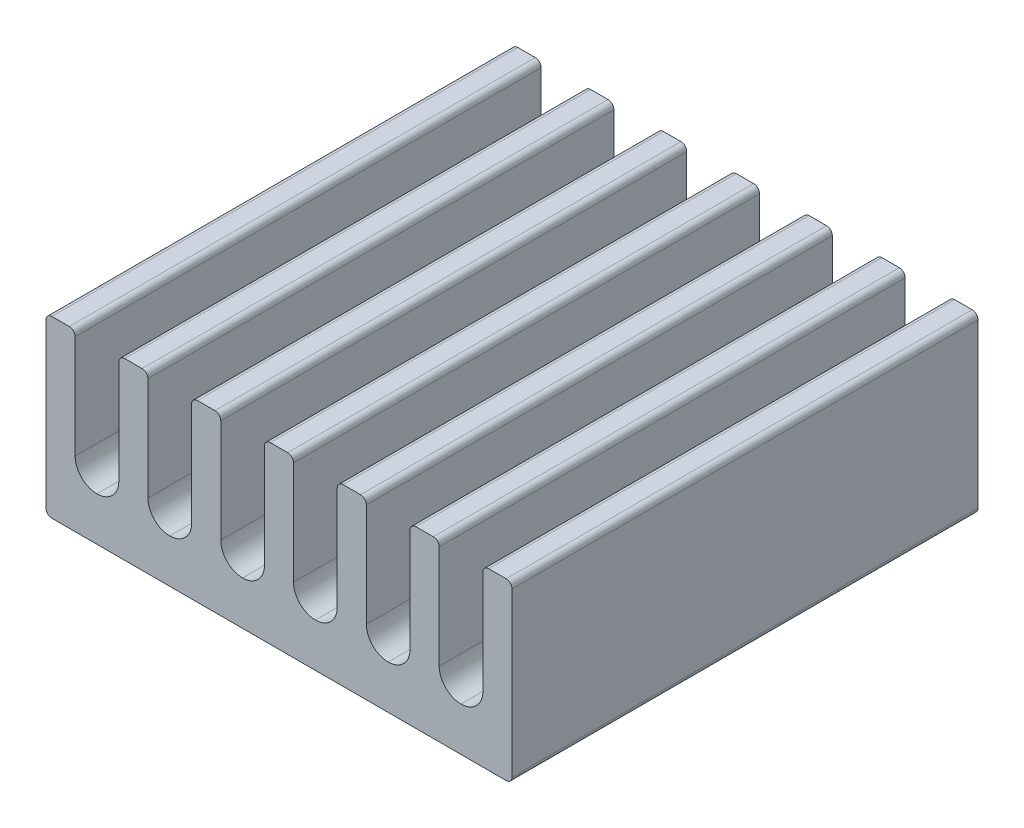
SolidWorks part; units mm, degrees
ref_plane "Front Plane" through (0, 0, 0) normal (0, 0, 1) x (1, 0, 0)
ref_plane "Top Plane" through (0, 0, 0) normal (0, 1, 0) x (1, 0, 0)
ref_plane "Right Plane" through (0, 0, 0) normal (1, 0, 0) x (0, 0, -1)
sketch "Sketch2" plane through (0, 0, 0) normal (0, 1, 0) x (1, 0, 0)
  line L1 (-8, -8) -> (8, -8)
  line L2 (-8, -8) -> (-8, 8)
  line L3 (-8, 8) -> (8, 8)
  line L4 (8, -8) -> (8, 8)
  line L5 (-8, -8) -> (8, 8) construction
  line L6 (-8, 8) -> (8, -8) construction
  point P0 (0, 0)
  dimension "D1" = 16
extrude "Boss-Extrude1" add sketch "Sketch2" along normal blind 1.5 contours L2 L1 L4 L3
sketch "Sketch3" plane through (0, 0, 8) normal (0, 0, 1) x (1, 0, 0)
  line L0 (-8, 0) -> (8, 0) construction
  line L1 (-8, 1.5) -> (-7, 1.5)
  line L2 (-8, 1.5) -> (-8, 6)
  line L3 (-8, 6) -> (-7, 6)
  line L4 (-7, 1.5) -> (-7, 6)
  line L5 (-5.5, 1.5) -> (-5.5, 6)
  line L6 (-5.5, 1.5) -> (-4.5, 1.5)
  line L7 (-4.5, 1.5) -> (-4.5, 6)
  line L8 (-5.5, 6) -> (-4.5, 6)
  line L9 (-3, 1.5) -> (-3, 6)
  line L10 (-3, 1.5) -> (-2, 1.5)
  line L11 (-2, 1.5) -> (-2, 6)
  line L12 (-3, 6) -> (-2, 6)
  line L13 (-0.5, 1.5) -> (-0.5, 6)
  line L14 (-0.5, 1.5) -> (0.5, 1.5)
  line L15 (0.5, 1.5) -> (0.5, 6)
  line L16 (-0.5, 6) -> (0.5, 6)
  line L17 (2, 1.5) -> (2, 6)
  line L18 (2, 1.5) -> (3, 1.5)
  line L19 (3, 1.5) -> (3, 6)
  line L20 (2, 6) -> (3, 6)
  line L21 (4.5, 1.5) -> (4.5, 6)
  line L22 (4.5, 1.5) -> (5.5, 1.5)
  line L23 (5.5, 1.5) -> (5.5, 6)
  line L24 (4.5, 6) -> (5.5, 6)
  line L25 (7, 1.5) -> (7, 6)
  line L26 (7, 1.5) -> (8, 1.5)
  line L27 (8, 1.5) -> (8, 6)
  line L28 (7, 6) -> (8, 6)
  point P7 (8, 2)
  dimension "D1" = 6
  dimension "D2" = 7
  dimension "D3" = 1
extrude "Boss-Extrude2" add sketch "Sketch3" against normal up to surface (16 mm away) up to face at (0, 0.75, -8)
fillet "Fillet1" radius 0.75 12 edges at (7, 1.5, 0) (5.5, 1.5, 0) (4.5, 1.5, 0) (3, 1.5, 0) (2, 1.5, 0) (0.5, 1.5, 0) (-0.5, 1.5, 0) (-2, 1.5, 0) (-3, 1.5, 0) (-4.5, 1.5, 0) (-5.5, 1.5, 0) (-7, 1.5, 0)
fillet "Fillet2" radius 0.2 16 edges at (8, 0, 0) (8, 6, 0) (7, 6, 0) (5.5, 6, 0) (4.5, 6, 0) (3, 6, 0) (2, 6, 0) (0.5, 6, 0) (-0.5, 6, 0) (-2, 6, 0) (-3, 6, 0) (-4.5, 6, 0) (-5.5, 6, 0) (-7, 6, 0) (-8, 0, 0) (-8, 6, 0)
